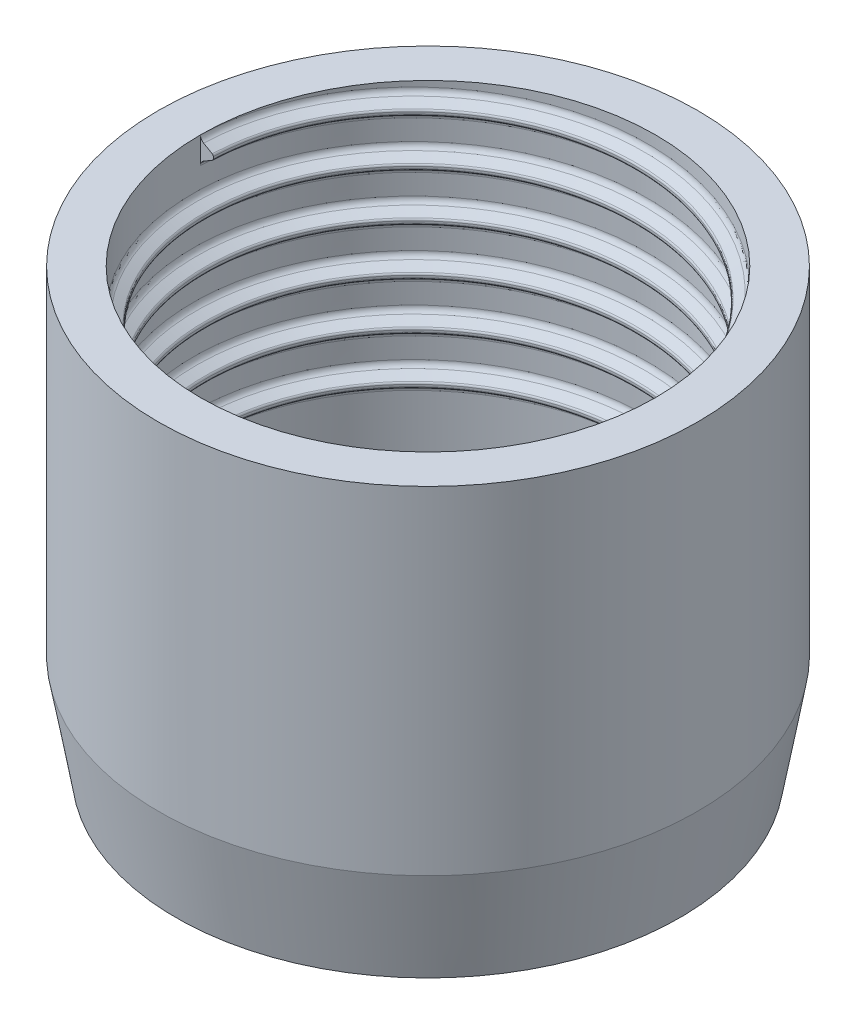
SolidWorks part; units mm, degrees
ref_plane "Front Plane" through (0, 0, 0) normal (0, 0, 1) x (1, 0, 0)
ref_plane "Top Plane" through (0, 0, 0) normal (0, 1, 0) x (1, 0, 0)
ref_plane "Right Plane" through (0, 0, 0) normal (1, 0, 0) x (0, 0, -1)
sketch "Sketch1" plane through (0, 0, 0) normal (0, 1, 0) x (1, 0, 0)
  circle A0 centre (0, 0) radius 16
extrude "Boss-Extrude1" add sketch "Sketch1" along normal blind 20 contours A0
sketch "Sketch2" plane through (0, 20, 0) normal (0, 1, 0) x (1, 0, 0)
  circle A0 centre (0, 0) radius 14
sketch "Sketch10" plane through (0, 20, 0) normal (0, 1, 0) x (1, 0, 0)
  circle A0 centre (0, 0) radius 13.5
extrude "Cut-Extrude2" cut sketch "Sketch10" against normal blind 20
thread "Thread1" pitch 2.1167 method extrude profile "Thread Profile2" start angle 0, offset 0, length 16, pitch 2.8, diameter 27
ref_plane "Plane2" through (-13.5, 20, 0) normal (0, 0, -1) x (1, 0, 0)
sketch "Thread Profile2" plane through (-13.5, 20, 0) normal (0, 0, -1) x (1, 0, 0)
  line L0 (0, 0) -> (0, 2.1167) construction
  line L1 (0, 0) -> (0, 1.5829)
  line L2 (0.381, 1.5829) -> (0.762, 1.5829) construction
  line L3 (0.762, 0.8497) -> (0.762, 0.7332)
  line L4 (0.6985, 0.9597) -> (0.1905, 1.253)
  line L5 (0.6985, 0.6232) -> (0.1905, 0.33)
  line L6 (0.381, 0) -> (0.762, 0) construction
  arc A0 (0.1905, 1.253) -> (0, 1.5829) centre (0.381, 1.5829) cw
  arc A1 (0.1905, 0.33) -> (0, 0) centre (0.381, 0) ccw
  arc A2 (0.762, 0.7332) -> (0.6985, 0.6232) centre (0.635, 0.7332) cw
  arc A3 (0.762, 0.8497) -> (0.6985, 0.9597) centre (0.635, 0.8497) ccw
  point P10 (0.762, 0.923)
  point P17 (0.762, 0.6599)
  point P18 (0, 1.363)
  point P19 (0, 0.22)
  point P20 (0, 0)
  dimension "RootFillet1" = 0.381
  dimension "RootFillet2" = 0.381
  dimension "CrestFillet2" = 0.127
  dimension "CrestFillet1" = 0.127
  dimension "Pitch" = 2.1167
  dimension "Angle1" = 30
  dimension "Angle2" = 30
  dimension "a" = 1.143
  dimension "b" = 0.762
  dimension "c" = 0.2631
sketch "Sketch19" plane through (0, 0, 0) normal (0, -1, 0) x (-1, 0, 0)
  circle A0 centre (0, 0) radius 13
  circle A1 centre (0, 0) radius 6.55
sketch "Sketch20" plane through (0, 0, 0) normal (0, -1, 0) x (1, 0, 0)
  circle A0 centre (0, 0) radius 16
extrude "Boss-Extrude3" add sketch "Sketch20" along normal blind 6 draft 10
extrude "Cut-Extrude3" cut sketch "Sketch19" along normal blind 3 contours A1
sketch "Sketch127" plane through (0, -3, 0) normal (0, 1, 0) x (1, 0, 0)
  circle A0 centre (0, 0) radius 5
extrude "Cut-Extrude4" cut sketch "Sketch127" against normal blind 3
